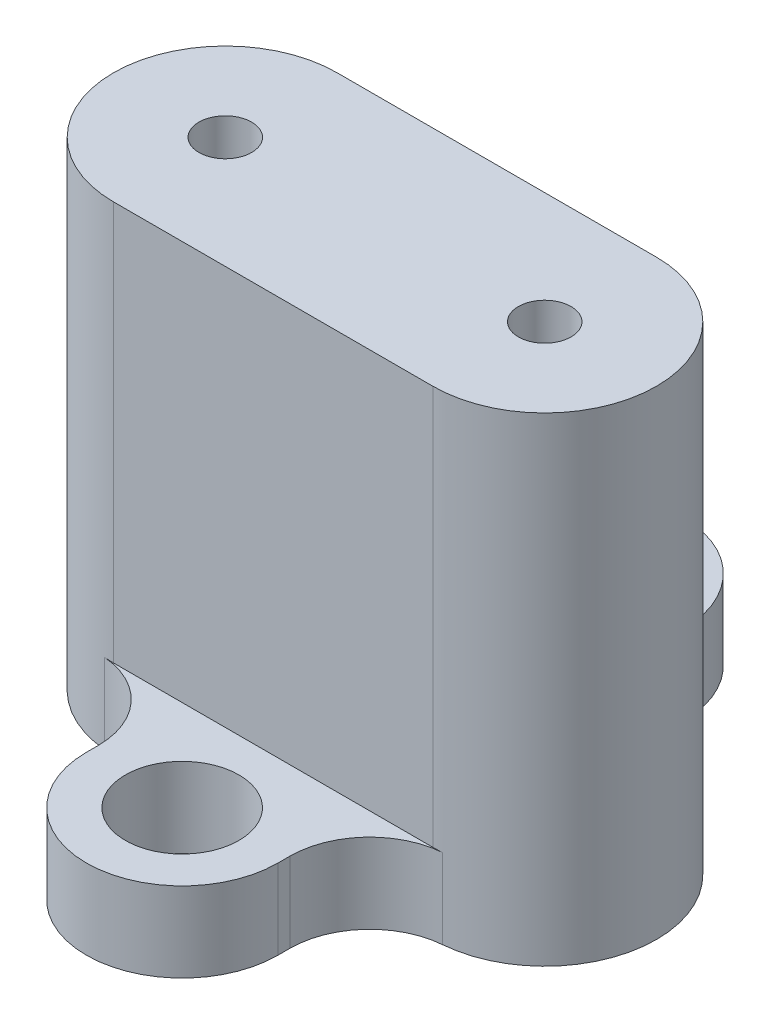
SolidWorks part; units mm, degrees
ref_plane "Front Plane" through (0, 0, 0) normal (0, 0, 1) x (1, 0, 0)
ref_plane "Top Plane" through (0, 0, 0) normal (0, 1, 0) x (1, 0, 0)
ref_plane "Right Plane" through (0, 0, 0) normal (1, 0, 0) x (0, 0, -1)
sketch "Sketch1" plane through (0, 0, 0) normal (0, 1, 0) x (1, 0, 0)
  line L0 (-10, 0) -> (10, 0) construction
  line L1 (-10, -7) -> (10, -7)
  line L2 (-10, 7) -> (10, 7)
  arc A0 (-10, 7) -> (-10, -7) centre (-10, 0) ccw
  arc A1 (10, -7) -> (10, 7) centre (10, 0) ccw
  dimension "D1" = 14
  dimension "D2" = 20
extrude "Boss-Extrude1" add sketch "Sketch1" along normal blind 30
hole_wizard "M4x0.7 Tapped Hole1" positions "Sketch2" profile "Sketch3" tap size "M4x0.7" standard "ANSI Metric"
sketch "Sketch2" plane through (0, 30, 0) normal (0, 1, 0) x (1, 0, 0)
  point P0 (-10, 0)
  point P3 (10, 0)
sketch "Sketch3" plane through (-10, 30, 0) normal (1, 0, 0) x (0, 0, 1)
  line L0 (0, 0) -> (0, 11.0914)
  line L1 (0, 11.0914) -> (1.65, 10.1)
  line L2 (1.65, 10.1) -> (1.65, 0)
  line L5 (1.65, 0) -> (0, 0)
  line L10 (0, 11.0914) -> (-1.65, 10.1) construction
  line L11 (0, -6.35) -> (0, 107.95) construction
  dimension "Tap Drill Dia." = 3.3
  dimension "Tap Drill Depth" = 10.1
  dimension "Drill Angle" = 118
cosmetic thread "Hole Thread1" parameters "D1"=8, "D2"=4
cosmetic thread "Hole Thread2" parameters "D1"=8, "D2"=4
sketch "Sketch4" plane through (0, 0, 0) normal (0, -1, 0) x (1, 0, 0)
  line L0 (0, 12.7) -> (0, -12.7) construction
  line L1 (6, 12.7) -> (6, -12.7)
  line L2 (-6, 12.7) -> (-6, -12.7)
  arc A0 (6, 12.7) -> (-6, 12.7) centre (0, 12.7) ccw
  arc A1 (-6, -12.7) -> (6, -12.7) centre (0, -12.7) ccw
  circle A2 centre (0, 12.7) radius 3.556
  circle A3 centre (0, -12.7) radius 3.556
  point P2 (0, 0)
  dimension "D1" = 7.112
  dimension "D2" = 6
  dimension "D3" = 25.4
extrude "Boss-Extrude2" add sketch "Sketch4" against normal blind 5
fillet "Fillet1" radius 5 4 edges at (-6, 2.5, 7) (-6, 2.5, -7) (6, 2.5, -7) (6, 2.5, 7)
